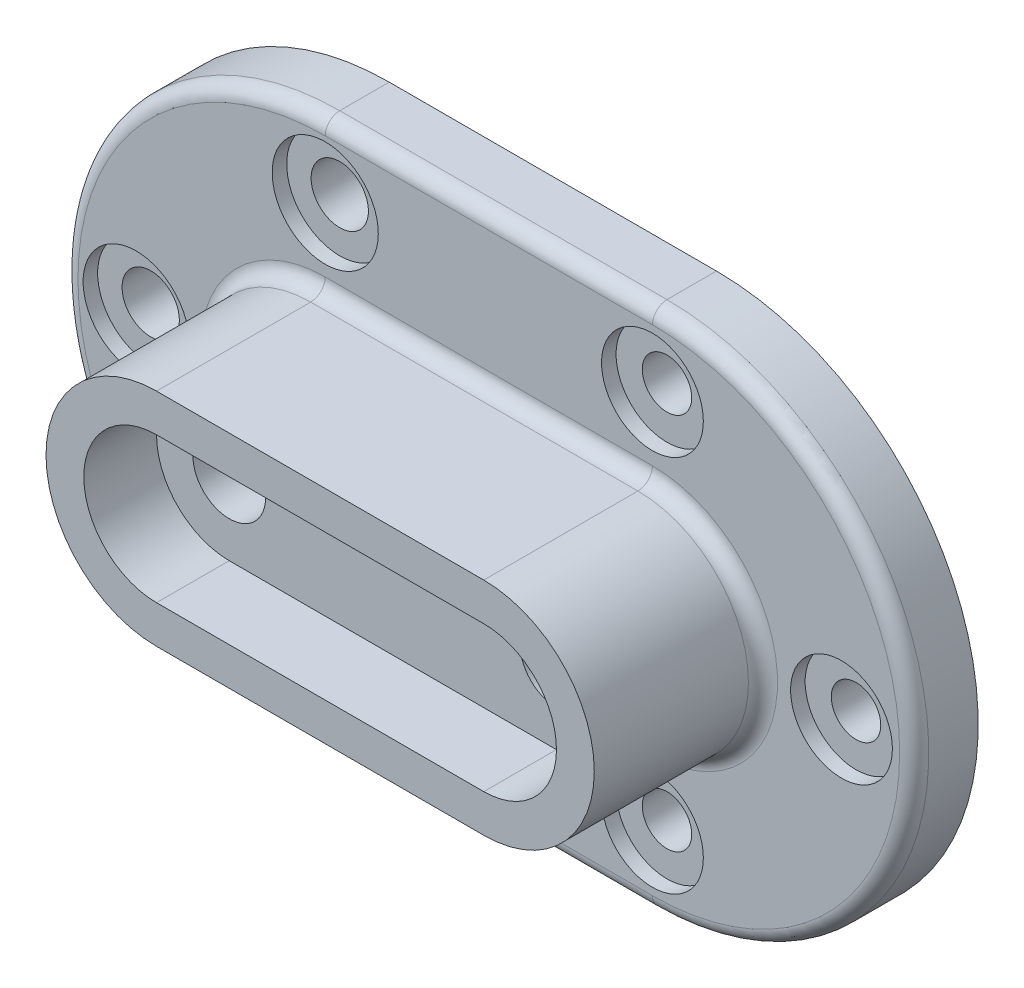
SolidWorks part; units mm, degrees
ref_plane "Front Plane" through (0, 0, 0) normal (0, 0, 1) x (1, 0, 0)
ref_plane "Top Plane" through (0, 0, 0) normal (0, 1, 0) x (1, 0, 0)
ref_plane "Right Plane" through (0, 0, 0) normal (1, 0, 0) x (0, 0, -1)
sketch "Sketch1" plane through (0, 0, 0) normal (0, 0, 1) x (1, 0, 0)
  line L0 (0, 0) -> (22.5, 0)
  line L1 (0, -18) -> (22.5, -18)
  line L2 (0, 18) -> (22.5, 18)
  line L3 (0, -7.6) -> (22.5, -7.6)
  line L4 (0, 7.6) -> (22.5, 7.6)
  line L5 (0, -5) -> (22.5, -5)
  line L6 (0, 5) -> (22.5, 5)
  line L7 (0, -13) -> (22.5, -13) construction
  line L8 (0, 13) -> (22.5, 13) construction
  arc A0 (22.5, -18) -> (22.5, 18) centre (22.5, 0) ccw
  arc A1 (0, 18) -> (0, -18) centre (0, 0) ccw
  arc A2 (0, 7.6) -> (0, -7.6) centre (0, 0) ccw
  arc A3 (22.5, -7.6) -> (22.5, 7.6) centre (22.5, 0) ccw
  arc A4 (0, 5) -> (0, -5) centre (0, 0) ccw
  arc A5 (22.5, -5) -> (22.5, 5) centre (22.5, 0) ccw
  arc A6 (0, 13) -> (0, -13) centre (0, 0) ccw construction
  arc A7 (22.5, -13) -> (22.5, 13) centre (22.5, 0) ccw construction
  dimension "D1" = 36
  dimension "D3" = 36
  dimension "D5" = 13
  dimension "D6" = 5
  dimension "D2" = 22.5
  dimension "D4" = 10.4
extrude "Boss-Extrude1" add sketch "Sketch1" along normal blind 4.4 contours L2 A1 L1 A0 A3 L3 A2 L4 region at (-17.3131, 0, 0)
extrude "Boss-Extrude2" add sketch "Sketch1<3>" along normal blind 16 contours L3 A3 L4 A2 A5 L5 A4 L6 region at (-7.1935, 0, 0)
sketch "Sketch1<3>" plane through (0, 0, 0) normal (0, 0, 1) x (1, 0, 0) same geometry as "Sketch1"
extrude "Boss-Extrude3" add sketch "Sketch1<4>" along normal blind 11 contours L5 A5 L6 A4 region at (-4.66, 0, 0)
sketch "Sketch1<4>" plane through (0, 0, 0) normal (0, 0, 1) x (1, 0, 0) same geometry as "Sketch1"
sketch "Sketch2" plane through (0, 0, 11) normal (0, 0, 1) x (1, 0, 0)
  circle A0 centre (0, 0) radius 2.5
  circle A1 centre (22.5, 0) radius 2.5
  dimension "D1" = 5
  dimension "D2" = 5
extrude "Cut-Extrude1" cut sketch "Sketch2" against normal through all
sketch "Sketch3" plane through (0, 0, 4.4) normal (0, 0, 1) x (1, 0, 0)
  circle A0 centre (35.5, 0) radius 3.5
  arc A1 (22.5, -13) -> (22.5, 13) centre (22.5, 0) ccw construction
  circle A2 centre (35.5, 0) radius 1.7
  circle A3 centre (-13, 0) radius 3.6489
  arc A4 (0, 13) -> (0, -13) centre (0, 0) ccw construction
  circle A5 centre (-13, 0) radius 1.9704
  circle A12 centre (22.5, -13) radius 3.5
  circle A13 centre (22.5, -13) radius 1.7
  circle A14 centre (0, 13) radius 3.6489
  circle A15 centre (0, 13) radius 1.9704
  circle A18 centre (0, -13) radius 3.6489
  circle A19 centre (0, -13) radius 1.9704
  circle A20 centre (13, 0) radius 3.6489 [skipped]
  circle A21 centre (13, 0) radius 1.9704 [skipped]
  circle A24 centre (22.5, 13) radius 3.5
  circle A25 centre (22.5, 13) radius 1.7
  circle A26 centre (9.5, 0) radius 3.5 [skipped]
  circle A27 centre (9.5, 0) radius 1.7 [skipped]
  point P24 (40.5, -18)
  point P28 (22.5, 0)
  point P35 (0, 0)
  dimension "D1" = 7
  dimension "D2" = 3.4
  dimension "D4" = 4
  dimension "D3" = 4
extrude "Cut-Extrude2" cut sketch "Sketch3" against normal blind 1
extrude "Cut-Extrude3" cut sketch "Sketch3<3>" against normal through all contours A5 | A15 | A19 | A2 | A25 | A13 region at (35.5, 0, 4.4) region at (-13, 0, 4.4) region at (22.5, -13, 4.4) region at (0, 13, 4.4) region at (0, -13, 4.4) region at (22.5, 13, 4.4)
sketch "Sketch3<3>" plane through (0, 0, 4.4) normal (0, 0, 1) x (1, 0, 0) same geometry as "Sketch3"
fillet "Fillet1" radius 1 8 edges at (11.25, -18, 4.4) (-18, 0, 4.4) (11.25, 18, 4.4) (-7.6, 0, 4.4) (11.25, 7.6, 4.4) (30.1, 0, 4.4) (40.5, 0, 4.4) (11.25, -7.6, 4.4)
